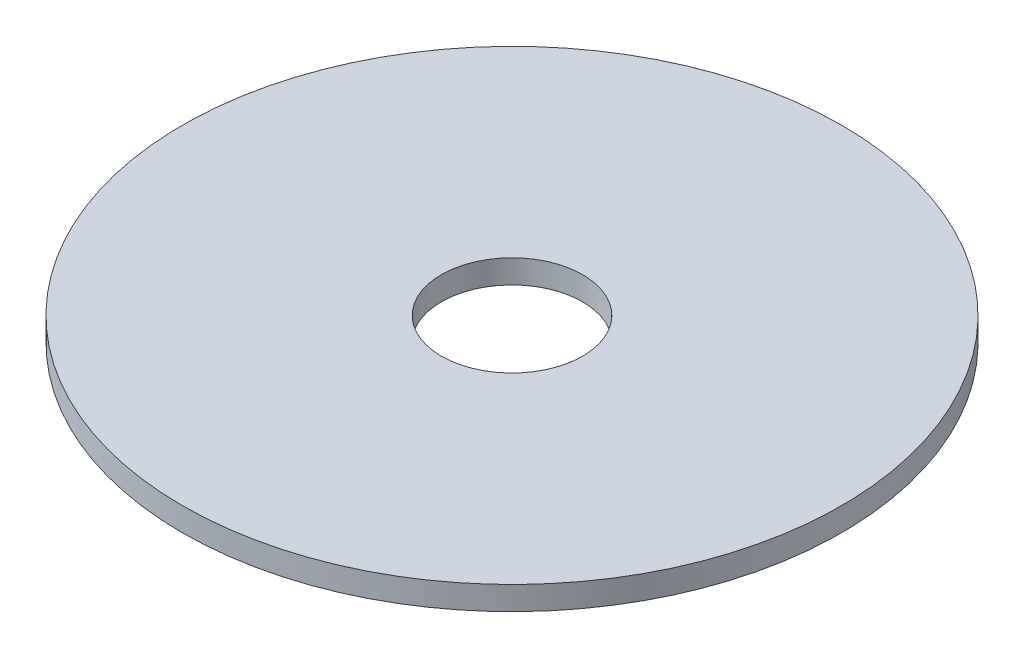
SolidWorks part; units mm, degrees
ref_plane "Front Plane" through (0, 0, 0) normal (0, 0, 1) x (1, 0, 0)
ref_plane "Top Plane" through (0, 0, 0) normal (0, 1, 0) x (1, 0, 0)
ref_plane "Right Plane" through (0, 0, 0) normal (1, 0, 0) x (0, 0, -1)
sketch "Sketch1" plane through (0, 0, 0) normal (0, 1, 0) x (1, 0, 0)
  circle A0 centre (0, 0) radius 70
  dimension "FLANGE_OD" = 140
extrude "Boss-Extrude1" add sketch "Sketch1" along normal blind 5
sketch "Sketch2" plane through (0, 0, 0) normal (0, 1, 0) x (1, 0, 0)
  circle A0 centre (0, 0) radius 15
  dimension "BORE_D" = 30
extrude "Cut-Extrude1" cut sketch "Sketch2" along normal through all
sketch "Sketch3" plane through (0, 5, 0) normal (0, 1, 0) x (1, 0, 0)
  circle A0 centre (0, 0) radius 11.9031 construction
  circle A1 centre (-11.9031, 0) radius 2.312
  dimension "BOLT_D" = 4.624
  dimension "BOLT_PCD" = 23.8061
extrude "Cut-Extrude2" cut sketch "Sketch3" against normal blind 4.8611 rebuild error yes
pattern_circular "CirPattern1" count 4 over 360 rebuild error yes
